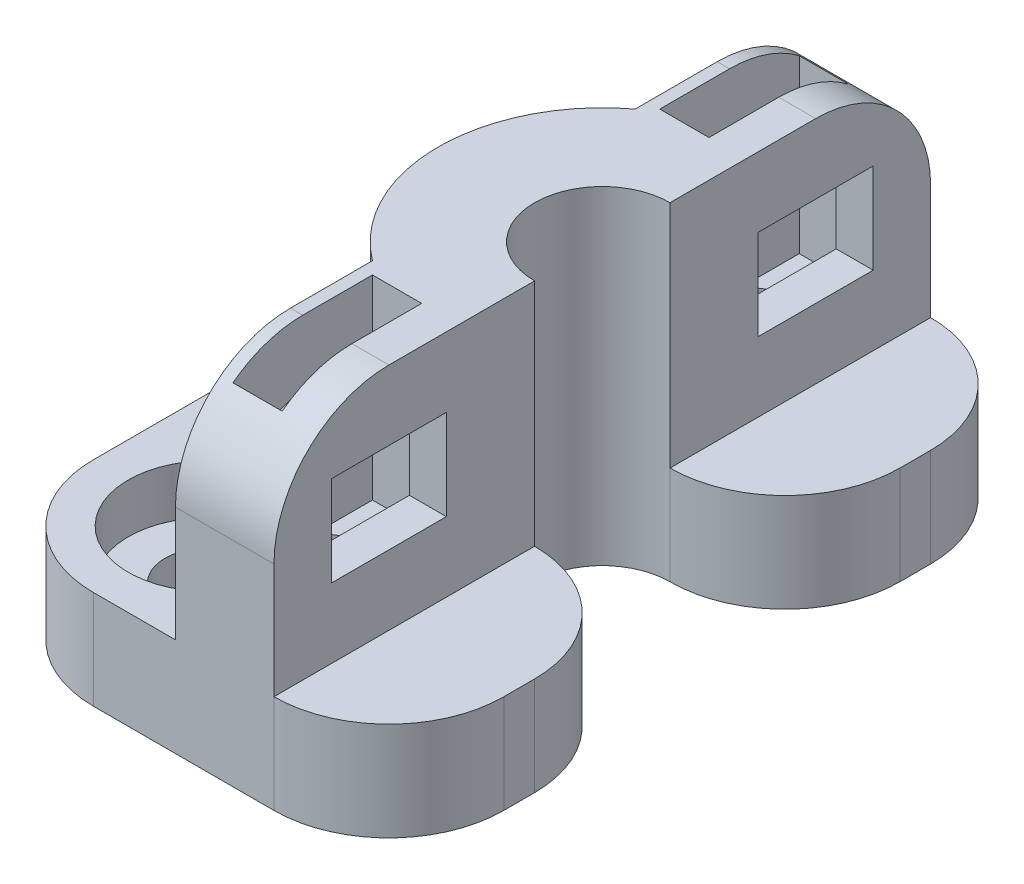
SolidWorks part; units mm, degrees
material "ABS"
ref_plane "Front Plane" through (0, 0, 0) normal (0, 0, 1) x (1, 0, 0)
ref_plane "Top Plane" through (0, 0, 0) normal (0, 1, 0) x (1, 0, 0)
ref_plane "Right Plane" through (0, 0, 0) normal (1, 0, 0) x (0, 0, -1)
sketch "Sketch1" plane through (0, 0, 0) normal (0, 1, 0) x (1, 0, 0)
  line L1 (-9, 20) -> (9, 20)
  line L2 (-9, 20) -> (-9, -20)
  line L3 (-9, -20) -> (9, -20)
  line L4 (9, 20) -> (9, -20)
  line L5 (-9, 20) -> (9, -20) construction
  line L6 (-9, -20) -> (9, 20) construction
  point P0 (0, 0)
  dimension "D1" = 18
  dimension "D2" = 40
extrude "Boss-Extrude1" add sketch "Sketch1" along normal blind 6
ref_axis "Axis1" through (9, 6, 0) along (0, 1, 0)
sketch "Sketch2" plane through (0, 6, 0) normal (0, 1, 0) x (1, 0, 0)
  line L0 (3, -20) -> (3, -8)
  line L1 (-9, -20) -> (9, -20) construction
  line L2 (3, 20) -> (3, 8)
  line L3 (9, 20) -> (-9, 20) construction
  line L4 (9, -20) -> (9, 20) construction
  line L9 (9, -20) -> (9, 20)
  line L10 (9, 20) -> (-9, 20)
  line L11 (-9, 20) -> (-9, -20)
  line L12 (-9, -20) -> (9, -20)
  line L13 (9, -20) -> (9, 20)
  line L14 (9, 20) -> (3, 20)
  line L16 (3, -20) -> (9, -20)
  arc A0 (3, 8) -> (3, -8) centre (9, 0) ccw
  dimension "D2" = 10
  dimension "D1" = 6
  dimension "D3" = 0
extrude "Boss-Extrude2" add sketch "Sketch2" along normal blind 14
sketch "Sketch3" plane through (0, 20, 0) normal (0, 1, 0) x (1, 0, 0)
  line L0 (9, -20) -> (9, 20) construction
  circle A0 centre (9, 0) radius 4.125
  dimension "D1" = 8.25
extrude "Cut-Extrude1" cut sketch "Sketch3" against normal through all
fillet "Fillet1" radius 7 2 edges at (6, 20, 20) (6, 20, -20)
sketch "Sketch12" plane through (0, 20, 0) normal (0, 1, 0) x (1, 0, 0)
  line L0 (16, 13) -> (9, 13) construction
  line L1 (3.75, 17.25) -> (6.75, 17.25)
  line L2 (3.75, 17.25) -> (3.75, 8.75)
  line L3 (3.75, 8.75) -> (6.75, 8.75)
  line L4 (6.75, 17.25) -> (6.75, 8.75)
  line L5 (3.75, 17.25) -> (6.75, 8.75) construction
  line L6 (3.75, 8.75) -> (6.75, 17.25) construction
  line L7 (9, 4.125) -> (9, 13) construction
  line L8 (0, 0) -> (24.0862, 0) construction
  line L9 (3.75, -8.75) -> (6.75, -17.25) construction
  line L10 (3.75, -17.25) -> (6.75, -8.75) construction
  line L11 (6.75, -17.25) -> (6.75, -8.75)
  line L12 (3.75, -8.75) -> (6.75, -8.75)
  line L13 (3.75, -17.25) -> (3.75, -8.75)
  line L14 (3.75, -17.25) -> (6.75, -17.25)
  point P0 (5.25, 13)
  point P16 (5.25, -13)
  dimension "D1" = 3
  dimension "D2" = 8.5
  dimension "D3" = 2.25
extrude "Cut-Extrude7" cut sketch "Sketch12" against normal blind 11.875
sketch "Sketch13" plane through (0, 8.125, 0) normal (0, 1, 0) x (1, 0, 0)
  line L0 (0, 0) -> (25.8503, 0) construction
  line L1 (6.75, 8.75) -> (6.75, 17.25) construction
  line L2 (6.75, 17.25) -> (3.75, 17.25) construction
  circle A0 centre (5.25, 13) radius 1.5
  circle A1 centre (5.25, -13) radius 1.5
  point P7 (6.75, 13)
  point P10 (5.25, 17.25)
  dimension "D1" = 3
extrude "Cut-Extrude8" cut sketch "Sketch13" against normal through all
sketch "Sketch14" plane through (3, 0, 0) normal (-1, 0, 0) x (0, 0, 1)
  line L0 (0, 0) -> (0, 34.28) construction
  line L1 (-20, 13) -> (-20, 6) construction
  line L2 (-13, 20) -> (-8, 20) construction
  circle A0 centre (-13, 13) radius 3
  circle A1 centre (13, 13) radius 3
  dimension "D1" = 6
  dimension "D2" = 7
  dimension "D3" = 7
extrude "Cut-Extrude9" cut sketch "Sketch14" against normal up to next
sketch "Sketch15" plane through (9, 0, 0) normal (1, 0, 0) x (0, 0, -1)
  line L0 (4.125, 20) -> (13, 20) construction
  line L1 (9.5, 15.75) -> (16.5, 15.75)
  line L2 (9.5, 15.75) -> (9.5, 10.25)
  line L3 (9.5, 10.25) -> (16.5, 10.25)
  line L4 (16.5, 15.75) -> (16.5, 10.25)
  line L5 (9.5, 15.75) -> (16.5, 10.25) construction
  line L6 (9.5, 10.25) -> (16.5, 15.75) construction
  line L7 (20, 13) -> (20, 0) construction
  line L8 (0, 0) -> (0, 22.7406) construction
  line L9 (-9.5, 10.25) -> (-16.5, 15.75) construction
  line L10 (-9.5, 15.75) -> (-16.5, 10.25) construction
  line L11 (-16.5, 15.75) -> (-16.5, 10.25)
  line L12 (-9.5, 10.25) -> (-16.5, 10.25)
  line L13 (-9.5, 15.75) -> (-9.5, 10.25)
  line L14 (-9.5, 15.75) -> (-16.5, 15.75)
  point P0 (13, 13)
  point P16 (-13, 13)
  dimension "D1" = 7
  dimension "D2" = 7
  dimension "D3" = 7
  dimension "D4" = 5.5
extrude "Cut-Extrude10" cut sketch "Sketch15" against normal up to next
sketch "Sketch7" plane through (9, 0, 0) normal (1, 0, 0) x (0, 0, -1)
  line L0 (-4.125, 0) -> (-4.125, 20) construction
  line L1 (-20, 0) -> (-4.125, 0)
  line L2 (-20, 0) -> (-20, 6)
  line L3 (-20, 6) -> (-4.125, 6)
  line L4 (-4.125, 0) -> (-4.125, 6)
  line L5 (0, 0) -> (0, 22.2367) construction
  line L6 (4.125, 0) -> (4.125, 6)
  line L7 (20, 6) -> (4.125, 6)
  line L8 (20, 0) -> (20, 6)
  line L9 (20, 0) -> (4.125, 0)
extrude "Boss-Extrude3" add sketch "Sketch7" along normal blind 7
fillet "Fillet2" radius 7 6 edges at (-9, 3, -20) (16, 3, -20) (16, 3, 20) (-9, 3, 20) (16, 3, -4.125) (16, 3, 4.125)
sketch "Sketch8" plane through (0, 6, 0) normal (0, 1, 0) x (1, 0, 0)
  line L0 (0, 0) -> (-13.0298, 0) construction
  circle A0 centre (-2, 13) radius 2.625
  circle A1 centre (-2, -13) radius 2.625
  dimension "D1" = 5.25
extrude "Cut-Extrude4" cut sketch "Sketch8" against normal through all
sketch "Sketch9" plane through (0, 0, 0) normal (0, 0, 1) x (1, 0, 0)
  line L0 (-9, 6) -> (2, 17)
  line L1 (2, 17) -> (2, 6)
  line L2 (-2, 6) -> (3, 6) construction
  line L3 (2, 6) -> (-9, 6)
  dimension "D1" = 45
  dimension "D2" = 11
extrude "Boss-Extrude4" add sketch "Sketch9" along normal blind 2.5 and the other way blind 2.5
sketch "Sketch10" plane through (0, 6, 0) normal (0, 1, 0) x (1, 0, 0)
  line L0 (0, 0) -> (-21.7297, 0) construction
  circle A0 centre (-2, 13) radius 4.875
  circle A1 centre (-2, -13) radius 4.875
  dimension "D1" = 9.75
extrude "Cut-Extrude5" cut sketch "Sketch10" against normal blind 3
